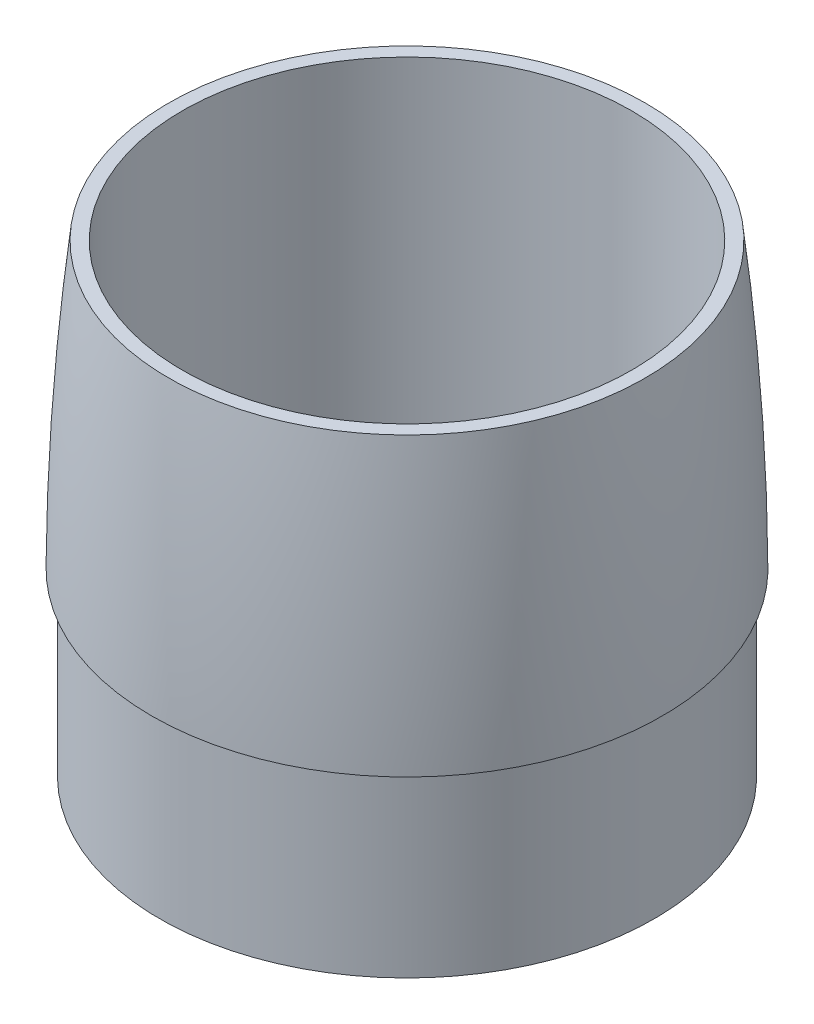
SolidWorks part; units mm, degrees
ref_plane "Front Plane" through (0, 0, 0) normal (0, 0, 1) x (1, 0, 0)
ref_plane "Top Plane" through (0, 0, 0) normal (0, 1, 0) x (1, 0, 0)
ref_plane "Right Plane" through (0, 0, 0) normal (1, 0, 0) x (0, 0, -1)
sketch "Croquis1" plane through (0, 0, 0) normal (1, 0, 0) x (0, 0, -1)
  line L0 (0, 0) -> (0, 290) construction
  line L1 (50, 12) -> (50, 103.2346)
  line L3 (55, 40) -> (55, 0)
  line L4 (55, 0) -> (50, 0)
  line L5 (55, 40) -> (56.8, 40)
  line L6 (0, 290) -> (0, 282.879)
  line L7 (50, 0) -> (0, 0)
  line L8 (0, 0) -> (0, 12)
  line L9 (0, 12) -> (50, 12)
  arc A0 (56.8, 40) -> (0, 290) centre (-538.8692, 36.1164) ccw
  arc A1 (50, 103.2346) -> (0, 282.879) centre (-538.8692, 36.1164) ccw
  arc A2 (53.8001, 39.9804) -> (-2.7139, 288.7214) centre (-538.8692, 36.1164) ccw construction
  dimension "D7" = 595.6818
  dimension "D1" = 110
  dimension "D2" = 1.8
  dimension "D3" = 5
  dimension "D4" = 250
  dimension "D5" = 40
  dimension "D8" = 12
  dimension "D6" = 3
revolve "Revolución1" add sketch "Croquis1" angle 360 about L0
ref_plane "Plano1" through (0, 103.2346, 0) normal (0, -1, 0) x (-1, 0, 0)
sketch "Croquis3" plane through (0, 103.2346, 0) normal (0, -1, 0) x (-1, 0, 0)
  circle A0 centre (0, 0) radius 68.8953
extrude "Cortar-Extruir3" cut sketch "Croquis3" against normal through all
equation "\"R\"= ( \"L\" ^ 2 + \"Rn\" ^ 2 ) / ( 2 * \"Rn\" )"
equation "\"D7@Croquis1\"=\"R\""
equation "\"L\"=250"
equation "\"D4@Croquis1\"=\"L\""
equation "\"Diameter\"=110"
equation "\"D1@Croquis1\"=\"Diameter\""
equation "\"Rn\"= \"Diameter\" / 2"
